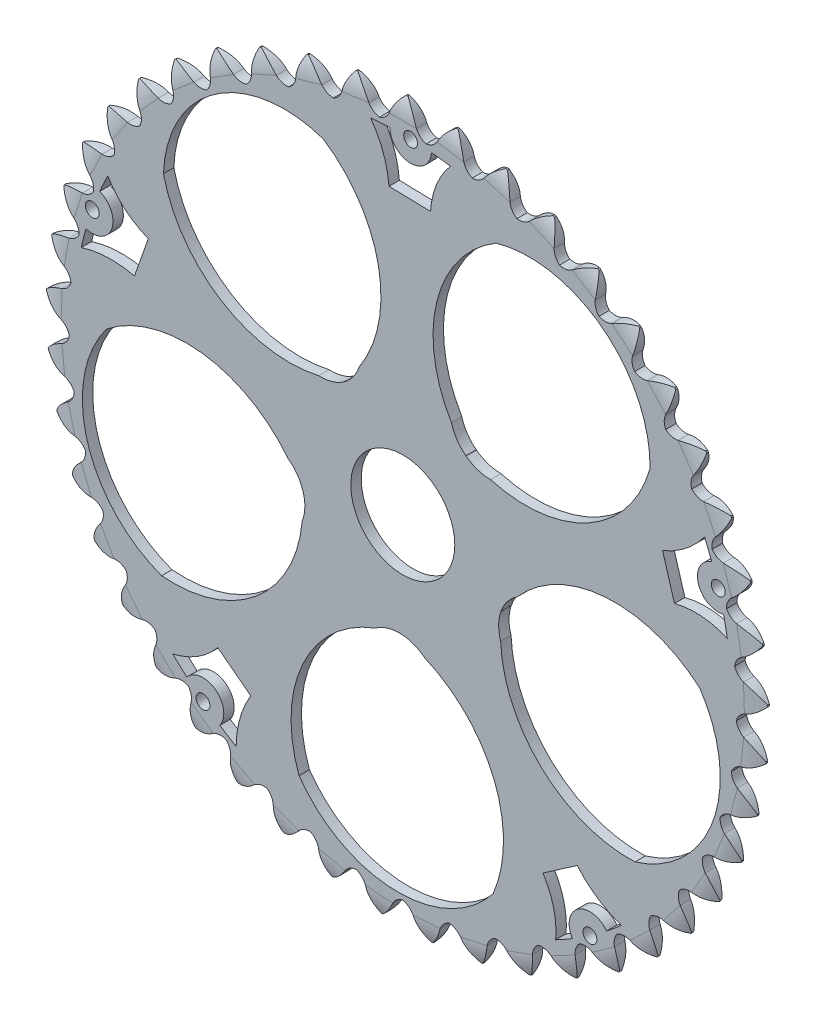
SolidWorks part; units mm, degrees
material "铸造合金钢"
ref_plane "前视基准面" through (0, 0, 0) normal (0, 0, 1) x (1, 0, 0)
ref_plane "上视基准面" through (0, 0, 0) normal (0, 1, 0) x (1, 0, 0)
ref_plane "右视基准面" through (0, 0, 0) normal (1, 0, 0) x (0, 0, -1)
sketch "草图1" plane through (0, 0, 0) normal (0, 0, 1) x (1, 0, 0)
  line L1 (-8.795, -8.3548) -> (2.3351, 2.7753)
  line L2 (2.3351, 2.7753) -> (11.587, 15.5095)
  line L3 (11.587, 15.5095) -> (18.733, 29.5343)
  line L4 (18.733, 29.5343) -> (23.597, 44.5042)
  line L5 (23.597, 44.5042) -> (26.0593, 60.0508)
  line L6 (26.0593, 60.0508) -> (26.0593, 75.7911)
  line L7 (26.0593, 75.7911) -> (23.597, 91.3376)
  line L8 (23.597, 91.3376) -> (18.733, 106.3076)
  line L9 (18.733, 106.3076) -> (11.587, 120.3324)
  line L10 (11.587, 120.3324) -> (2.3351, 133.0666)
  line L11 (2.3351, 133.0666) -> (-8.795, 144.1967)
  line L12 (-8.795, 144.1967) -> (-21.5292, 153.4486)
  line L13 (-21.5292, 153.4486) -> (-35.554, 160.5946)
  line L14 (-35.554, 160.5946) -> (-50.5239, 165.4586)
  line L15 (-50.5239, 165.4586) -> (-66.0705, 167.9209)
  line L16 (-66.0705, 167.9209) -> (-81.8108, 167.9209)
  line L17 (-81.8108, 167.9209) -> (-97.3574, 165.4586)
  line L18 (-97.3574, 165.4586) -> (-112.3273, 160.5946)
  line L19 (-112.3273, 160.5946) -> (-126.3521, 153.4486)
  line L20 (-126.3521, 153.4486) -> (-139.0863, 144.1967)
  line L21 (-139.0863, 144.1967) -> (-150.2164, 133.0666)
  line L22 (-150.2164, 133.0666) -> (-159.4683, 120.3324)
  line L23 (-159.4683, 120.3324) -> (-166.6143, 106.3076)
  line L24 (-166.6143, 106.3076) -> (-171.4783, 91.3376)
  line L25 (-171.4783, 91.3376) -> (-173.9407, 75.7911)
  line L26 (-173.9407, 75.7911) -> (-173.9407, 60.0508)
  line L27 (-173.9407, 60.0508) -> (-171.4783, 44.5042)
  line L28 (-171.4783, 44.5042) -> (-166.6143, 29.5343)
  line L29 (-166.6143, 29.5343) -> (-159.4683, 15.5095)
  line L30 (-159.4683, 15.5095) -> (-150.2164, 2.7753)
  line L31 (-150.2164, 2.7753) -> (-139.0863, -8.3548)
  line L32 (-139.0863, -8.3548) -> (-126.3521, -17.6067)
  line L33 (-126.3521, -17.6067) -> (-112.3273, -24.7527)
  line L34 (-112.3273, -24.7527) -> (-97.3574, -29.6167)
  line L35 (-97.3574, -29.6167) -> (-81.8108, -32.0791)
  line L36 (-81.8108, -32.0791) -> (-66.0705, -32.0791)
  line L37 (-66.0705, -32.0791) -> (-50.5239, -29.6167)
  line L38 (-50.5239, -29.6167) -> (-35.554, -24.7527)
  line L39 (-35.554, -24.7527) -> (-21.5292, -17.6067)
  line L40 (-21.5292, -17.6067) -> (-8.795, -8.3548)
  circle A0 centre (-73.9407, 67.9209) radius 100 construction
  point P1 (-73.9407, 167.9209)
  dimension "D1" = 100
sketch "草图5" plane through (0, 0, 0) normal (0, 0, 1) x (1, 0, 0)
  line L0 (-81.8108, 167.9209) -> (-73.9407, 67.9209) construction
  line L1 (-73.9407, 67.9209) -> (-73.9407, 172.3555) construction
  line L2 (-66.0705, 167.9209) -> (-81.8108, 167.9209) construction
  line L3 (-75.4407, 172.0301) -> (-78.9865, 163.9885) construction
  line L4 (-72.4407, 172.0301) -> (-68.7989, 163.9834) construction
  line L5 (-73.9407, 67.9209) -> (-73.9407, 39.2591)
  line L7 (-81.8108, 167.9209) -> (-81.8108, 172.0301) construction
  line L8 (-81.8108, 172.0301) -> (-66.0705, 172.0301) construction
  circle A0 centre (-73.9407, 67.9209) radius 96.2
  circle A1 centre (-81.8108, 167.9209) radius 1.55
  circle A2 centre (-66.0705, 167.9209) radius 1.55
  circle A3 centre (-66.0705, 167.9209) radius 4.1092
  circle A4 centre (-81.8108, 167.9209) radius 4.1092
  arc A5 (-79.9351, 171.5771) -> (-67.9462, 171.5771) centre (-73.9407, 183.2612) ccw
  arc A6 (-79.9351, 164.2648) -> (-67.9462, 164.2648) centre (-73.9407, 152.5807) cw
  arc A7 (-74.1907, 172.0301) -> (-77.8781, 166.4216) centre (-64.2356, 161.4686) ccw
  arc A8 (-77.8781, 166.4216) -> (-81.4884, 163.8244) centre (-81.8249, 168.1001) cw
  arc A10 (-70.0032, 166.4216) -> (-66.3929, 163.8244) centre (-66.0564, 168.1001) ccw
  arc A11 (-73.6907, 172.0301) -> (-70.0032, 166.4216) centre (-83.6457, 161.4686) cw
  point P17 (-73.9407, 167.9209)
  point P26 (-73.9407, 172.0301)
  dimension "D1" = 1.5
  dimension "D4" = 3.1
  dimension "D5" = 2.5019
  dimension "D2" = 1.5
  dimension "D3" = 0.25
sketch "草图6" plane through (0, 0, 0) normal (0, 0, 1) x (1, 0, 0)
  line L0 (-74.1907, 172.0301) -> (-73.6907, 172.0301)
  arc A0 (-74.1907, 172.0301) -> (-77.8781, 166.4216) centre (-64.2356, 161.4686) ccw construction
  arc A1 (-74.1907, 172.0301) -> (-77.8781, 166.4216) centre (-64.2356, 161.4686) ccw
  arc A2 (-81.4884, 163.8244) -> (-77.8781, 166.4216) centre (-81.8249, 168.1001) ccw construction
  arc A3 (-81.4884, 163.8244) -> (-77.8781, 166.4216) centre (-81.8249, 168.1001) ccw
  arc A4 (-70.0032, 166.4216) -> (-66.3929, 163.8244) centre (-66.0564, 168.1001) ccw construction
  arc A5 (-70.0032, 166.4216) -> (-73.6907, 172.0301) centre (-83.6457, 161.4686) ccw construction
  arc A6 (-70.0032, 166.4216) -> (-66.3929, 163.8244) centre (-66.0564, 168.1001) ccw
  arc A7 (-70.0032, 166.4216) -> (-73.6907, 172.0301) centre (-83.6457, 161.4686) ccw
sketch "草图7" plane through (0, 0, 0) normal (0, 0, 1) x (1, 0, 0)
  point P1 (-81.8108, 167.9209)
  dimension "D1" = 4.1092
sketch "草图10" plane through (0, 0, 0) normal (0, 0, 1) x (1, 0, 0)
  line L0 (-81.8108, 172.0301) -> (-66.0705, 172.0301) construction
  line L1 (-74.1907, 172.0301) -> (-73.6907, 172.0301)
  circle A0 centre (-73.9407, 67.9209) radius 96.2 construction
  arc A1 (-66.3929, 163.8244) -> (-81.4884, 163.8244) centre (-73.9407, 67.9209) ccw
  arc A2 (-74.1907, 172.0301) -> (-77.8781, 166.4216) centre (-64.2356, 161.4686) ccw construction
  arc A3 (-74.1907, 172.0301) -> (-77.8781, 166.4216) centre (-64.2356, 161.4686) ccw
  arc A4 (-70.0032, 166.4216) -> (-73.6907, 172.0301) centre (-83.6457, 161.4686) ccw construction
  arc A5 (-70.0032, 166.4216) -> (-73.6907, 172.0301) centre (-83.6457, 161.4686) ccw
  arc A6 (-81.4884, 163.8244) -> (-77.8781, 166.4216) centre (-81.8249, 168.1001) ccw construction
  arc A7 (-70.0032, 166.4216) -> (-66.3929, 163.8244) centre (-66.0564, 168.1001) ccw construction
  arc A8 (-81.4884, 163.8244) -> (-77.8781, 166.4216) centre (-81.8249, 168.1001) ccw
  arc A9 (-70.0032, 166.4216) -> (-66.3929, 163.8244) centre (-66.0564, 168.1001) ccw
extrude "凸台-拉伸1" add sketch "草图10" along normal mid plane 3
ref_plane "基准面1" through (-73.9407, 0, 0) normal (1, 0, 0) x (0, 0, -1)
sketch "草图18" plane through (-73.9407, 0, 0) normal (1, 0, 0) x (0, 0, -1)
  line L0 (-1.5, 172.0301) -> (1.5, 172.0301) construction
  line L1 (-1.5, 172.0301) -> (-1.5, 166.4216) construction
  line L2 (0, 166.4216) -> (0, 163.8244) construction
  line L3 (-1.5, 166.4216) -> (1.5, 166.4216) construction
  line L4 (-1.5, 163.8244) -> (1.5, 163.8244) construction
  line L5 (-0.25, 172.0301) -> (0.25, 172.0301)
  line L6 (-1.5, 166.4216) -> (1.5, 166.4216)
  line L7 (1.5, 166.4216) -> (2.3843, 166.4216)
  line L8 (2.3843, 166.4216) -> (2.3843, 173.3771)
  line L9 (2.3843, 173.3771) -> (-2.4464, 173.3771)
  line L10 (-2.4464, 173.3771) -> (-2.3843, 166.4216)
  line L11 (-2.3843, 166.4216) -> (-1.5, 166.4216)
  arc A0 (-1.5, 166.4216) -> (-0.25, 172.0301) centre (11.7073, 166.4216) cw
  arc A1 (1.5, 166.4216) -> (0.25, 172.0301) centre (-11.7073, 166.4216) ccw
  dimension "D1" = 0.25
extrude "切除-拉伸1" cut sketch "草图18" against normal blind 12 and the other way blind 12 contours A1 L7 L8 L9 L10 L11 A0 L5 region at (-73.9407, 169.3131, 1.2664)
sketch "草图19" plane through (0, 0, 0) normal (0, 0, 1) x (1, 0, 0)
  circle A0 centre (-73.9407, 67.9209) radius 96.2
pattern_circular "阵列(圆周)1" count 45 over 360 about axis through (-73.9407, 67.9209, 1.5) along (0, 0, -1) of "凸台-拉伸1", "切除-拉伸1"
extrude "凸台-拉伸2" add sketch "草图19" along normal mid plane 3 contours A0
sketch "草图21" plane through (0, 0, 0) normal (0, 0, 1) x (1, 0, 0)
  circle A0 centre (-73.9407, 67.9209) radius 30
extrude "切除-拉伸3" cut sketch "草图21" against normal through all both and the other way through all
sketch "草图23" plane through (0, 0, 1.5) normal (0, 0, 1) x (1, 0, 0)
  line L0 (-158.8086, 97.8781) -> (-73.9407, 67.9209)
  line L1 (-73.9407, 67.9209) -> (-71.6753, 157.8924)
  line L2 (-73.9407, 67.9209) -> (12.3261, 93.5733)
  line L8 (-77.9253, 148.0387) -> (-65.9287, 147.7526)
  line L9 (1.0246, 96.4683) -> (4.4596, 84.9705)
  line L10 (-23.6249, 5.4464) -> (-33.4986, -1.3735)
  line L11 (-117.8091, 0.7621) -> (-127.3463, 8.0451)
  line L12 (-151.3685, 88.8891) -> (-147.3892, 100.2101)
  arc A2 (-77.6715, 162.8476) -> (-83.1887, 162.4697) centre (-73.9407, 67.9209) ccw
  circle A4 centre (-73.9407, 67.9209) radius 95
  circle A5 centre (-71.6753, 162.8939) radius 2
  arc A6 (-65.6882, 162.5618) -> (-77.6715, 162.8476) centre (-71.6753, 162.8939) cw
  arc A7 (-65.6882, 162.5618) -> (-60.1786, 161.9188) centre (-73.9407, 67.9209) cw
  arc A8 (-83.1887, 162.4697) -> (-77.9253, 148.0387) centre (-106.472, 145.8023) cw
  arc A9 (-60.1786, 161.9188) -> (-65.9287, 147.7526) centre (-42.3459, 146.4303) ccw
  arc A10 (18.6183, 89.318) -> (15.1871, 100.8031) centre (17.0841, 95.1147) cw
  arc A11 (13.1228, 105.9335) -> (1.0246, 96.4683) centre (-9.9238, 122.9268) cw
  arc A12 (15.1871, 100.8031) -> (13.1228, 105.9335) centre (-73.9407, 67.9209) ccw
  arc A13 (19.7094, 83.8794) -> (4.4596, 84.9705) centre (10.4896, 62.1332) ccw
  circle A14 centre (-73.9407, 67.9209) radius 95
  circle A15 centre (17.0841, 95.1147) radius 2
  arc A16 (-24.9885, -13.4958) -> (-15.1258, -6.6835) centre (-19.9496, -10.2454) cw
  arc A17 (-10.8844, -3.1348) -> (-23.6249, 5.4464) centre (-1.8447, 24.035) cw
  arc A18 (-15.1258, -6.6835) -> (-10.8844, -3.1348) centre (-73.9407, 67.9209) ccw
  arc A19 (-29.8238, -16.2141) -> (-33.4986, -1.3735) centre (-53.3547, -14.1655) ccw
  circle A20 centre (-73.9407, 67.9209) radius 95
  circle A21 centre (-19.9496, -10.2454) radius 2
  arc A22 (-136.2456, -3.7945) -> (-126.7189, -11.0693) centre (-131.5971, -7.5823) cw
  arc A23 (-122.0332, -14.0065) -> (-117.8091, 0.7621) centre (-93.3997, -14.2079) cw
  arc A24 (-126.7189, -11.0693) -> (-122.0332, -14.0065) centre (-73.9407, 67.9209) ccw
  arc A25 (-140.325, -0.0358) -> (-127.3463, 8.0451) centre (-145.6481, 22.9764) ccw
  circle A26 centre (-73.9407, 67.9209) radius 95
  circle A27 centre (-131.5971, -7.5823) radius 2
  arc A28 (-161.3993, 105.0151) -> (-165.3742, 93.7067) centre (-163.5653, 99.4237) cw
  arc A29 (-166.7197, 88.3427) -> (-151.3685, 88.8891) centre (-158.063, 61.0484) cw
  arc A30 (-165.3742, 93.7067) -> (-166.7197, 88.3427) centre (-73.9407, 67.9209) ccw
  arc A31 (-159.0853, 110.0564) -> (-147.3892, 100.2101) centre (-138.8442, 122.2301) ccw
  circle A32 centre (-73.9407, 67.9209) radius 95
  circle A33 centre (-163.5653, 99.4237) radius 2
  point P65 (-73.9407, 67.9209)
  dimension "D1" = 6
  dimension "D2" = 6
  dimension "D3" = 5
extrude "切除-拉伸5" cut sketch "草图23" against normal through all contours A4 A5 | A4 A5 | A2 A8 L8 L1 A6 | A9 A4 A6 L1 L8 | A32 A33 | A32 A33 | A31 A26 A28 L0 L12 | A4 A29 L12 L0 A28 | A14 A15 | A14 A15 | A4 A11 L9 L2 A10 | A13 A4 A10 L2 L9 | A20 A21 | A20 A21 | A19 A14 A16 A4 A17 L10 | A26 A27 | A26 A27 | A25 A20 A22 A4 A23 L11 region at (-154.4616, 101.1633, 1.5) region at (-157.5218, 92.4321, 1.5) region at (-162.7609, 99.1409, 1.5) region at (-164.3625, 99.7039, 1.5) region at (-76.4571, 154.9857, 1.5) region at (-67.2076, 154.7733, 1.5) region at (8.0857, 97.2208, 1.5) region at (10.7401, 88.3578, 1.5) region at (-126.7062, -1.2313, 1.5) region at (-71.6552, 163.7387, 1.5) region at (-71.6956, 162.0415, 1.5) region at (-131.0796, -6.9047, 1.5) region at (-132.1099, -8.2539, 1.5) region at (16.2671, 94.8707, 1.5) region at (17.8937, 95.3566, 1.5) region at (-24.4785, -3.6313, 1.5) region at (-19.4694, -10.9407, 1.5) region at (-20.4342, -9.5438, 1.5)
sketch "草图26" plane through (0, 0, 0) normal (0, 0, 1) x (1, 0, 0)
  line L0 (-73.9407, 67.9209) -> (17.0841, 95.1147)
  line L1 (-73.9407, 67.9209) -> (-71.6753, 162.8939)
  line L2 (-73.9407, 67.9209) -> (-55.4764, 91.5656)
  arc A0 (17.0841, 95.1147) -> (-16.2842, 143.4242) centre (-73.9407, 67.9209) ccw
  circle A1 centre (-73.9407, 67.9209) radius 15
  circle A2 centre (-73.9407, 67.9209) radius 30
extrude "凸台-拉伸5" add sketch "草图26" along normal mid plane 3 contours L1 A2 L0 A1 | L2 A2 L1 A1 | L0 A2 L2 A1 region at (-54.9751, 80.8698, 0) region at (-52.1393, 73.5485, 0) region at (-66.2172, 89.5197, 0)
sketch "草图27" plane through (0, 0, 0) normal (0, 0, 1) x (1, 0, 0)
  arc A1 (-47.0346, 149.2908) -> (-2.5996, 115.1735) centre (-37.5072, 115.7044) cw
  arc A2 (-47.0346, 149.2908) -> (-55.7334, 91.7641) centre (-12.677, 114.6744) ccw
  arc A3 (-55.7334, 91.7641) -> (-2.5996, 115.1735) centre (-44.6169, 138.5374) ccw
  arc A5 (11.7612, 67.4764) -> (-6.9552, 14.6734) centre (-17.2373, 48.0365) cw
  arc A6 (11.7612, 67.4764) -> (-45.6381, 57.9727) centre (-10.5439, 24.1034) ccw
  arc A7 (-45.6381, 57.9727) -> (-6.9552, 14.6734) centre (2.2811, 61.8541) ccw
  arc A8 (-47.8801, -13.7237) -> (-103.8824, -12.2405) centre (-75.3295, 7.8483) cw
  arc A9 (-47.8801, -13.7237) -> (-74.656, 37.9295) centre (-96.0229, -5.9133) ccw
  arc A10 (-74.656, 37.9295) -> (-103.8824, -12.2405) centre (-56.1568, -6.4451) ccw
  arc A11 (-143.5362, 17.9063) -> (-159.4312, 71.626) centre (-131.5023, 50.6784) cw
  arc A12 (-143.5362, 17.9063) -> (-102.6853, 59.3334) centre (-150.985, 66.1064) ccw
  arc A13 (-102.6853, 59.3334) -> (-159.4312, 71.626) centre (-139.1714, 28.0271) ccw
  arc A14 (-143.0136, 118.6548) -> (-96.835, 150.3722) centre (-108.1268, 117.3371) cw
  arc A15 (-143.0136, 118.6548) -> (-90.9904, 92.605) centre (-99.4744, 140.6337) ccw
  arc A16 (-90.9904, 92.605) -> (-96.835, 150.3722) centre (-132.0394, 117.6312) ccw
  point P36 (-73.9407, 67.9209)
  dimension "D1" = 5
extrude "切除-拉伸6" cut sketch "草图27" against normal mid plane 3
sketch "草图29" plane through (0, 0, 0) normal (0, 0, 1) x (1, 0, 0)
  arc A1 (-96.835, 150.3722) -> (-86.5229, 98.6337) centre (-117.5482, 119.3469) cw
  arc A2 (-143.0136, 118.6548) -> (-98.2103, 90.561) centre (-106.565, 127.0096) ccw
  arc A3 (-98.2103, 90.561) -> (-86.5229, 98.6337) centre (-97.6291, 102.2162) ccw
  arc A4 (-47.0346, 149.2908) -> (-59.9084, 97.9989) centre (-27.8255, 117.2079) ccw
  arc A5 (-2.5996, 115.1735) -> (-48.6192, 89.3781) centre (-38.5071, 125.2856) cw
  arc A6 (-59.9084, 97.9989) -> (-48.6192, 89.3781) centre (-48.644, 101.0478) ccw
  arc A7 (11.7612, 67.4764) -> (-40.9986, 63.87) centre (-12.8156, 39.2933) ccw
  arc A8 (-6.9552, 14.6734) -> (-45.7089, 50.4695) centre (-8.434, 51.9483) cw
  arc A9 (-40.9986, 63.87) -> (-45.7089, 50.4695) centre (-34.618, 54.0992) ccw
  arc A10 (-47.8801, -13.7237) -> (-67.6136, 35.3394) centre (-82.2784, 0.9411) ccw
  arc A11 (-103.8824, -12.2405) -> (-81.8139, 35.6781) centre (-68.8888, 0.6846) cw
  arc A12 (-67.6136, 35.3394) -> (-81.8139, 35.6781) centre (-74.9346, 26.2517) ccw
  arc A13 (-143.5362, 17.9063) -> (-102.9723, 51.8353) centre (-140.2188, 55.1527) ccw
  arc A14 (-159.4312, 71.626) -> (-107.0383, 65.4453) centre (-136.3251, 42.3392) cw
  arc A15 (-102.9723, 51.8353) -> (-107.0383, 65.4453) centre (-113.8776, 55.9897) ccw
  point P42 (-73.9407, 67.9209)
  dimension "D1" = 5
extrude "切除-拉伸-薄壁1" cut sketch "草图29" against normal mid plane 10 thin thin type one direction wall 10
ref_plane "基准面2" through (-30.2798, 156.3043, 1.5) normal (0, 0, -1) x (-1, 0, 0)
